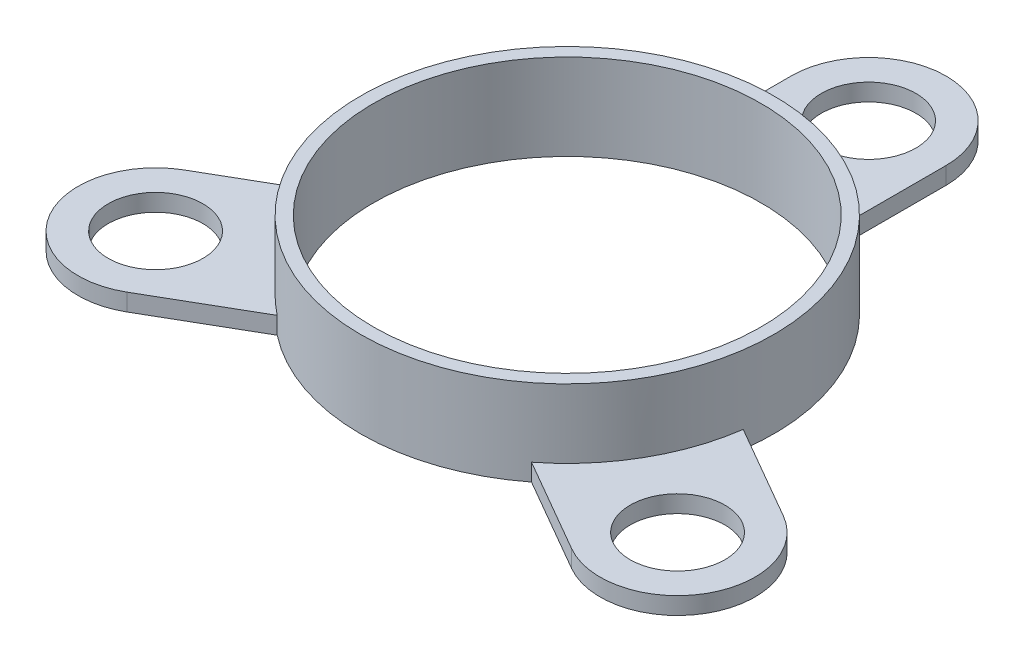
SolidWorks part; units mm, degrees
ref_plane "Front Plane" through (0, 0, 0) normal (0, 0, 1) x (1, 0, 0)
ref_plane "Top Plane" through (0, 0, 0) normal (0, 1, 0) x (1, 0, 0)
ref_plane "Right Plane" through (0, 0, 0) normal (1, 0, 0) x (0, 0, -1)
sketch "Sketch1" plane through (0, 0, 0) normal (0, 1, 0) x (1, 0, 0)
  line L0 (0, 0) -> (0, 22) construction
  line L1 (17.4054, -4.8529) -> (11.8839, -1.665)
  line L2 (12.9054, -12.6471) -> (7.3839, -9.4593)
  line L3 (-4.5, 17.5) -> (-4.5, 11.1243)
  line L4 (4.5, 17.5) -> (4.5, 11.1243)
  line L5 (-12.9054, -12.6471) -> (-7.3839, -9.4593)
  line L6 (-17.4054, -4.8529) -> (-11.8839, -1.665)
  circle A0 centre (0, 0) radius 22
  circle A1 centre (0, 0) radius 11.25
  circle A2 centre (0, 0) radius 4
  circle A3 centre (0, 0) radius 17.5 construction
  arc A4 (12.9054, -12.6471) -> (17.4054, -4.8529) centre (15.1554, -8.75) ccw
  circle A5 centre (15.1554, -8.75) radius 2.75
  circle A6 centre (0, 17.5) radius 2.75 construction
  arc A7 (-17.4054, -4.8529) -> (-12.9054, -12.6471) centre (-15.1554, -8.75) ccw
  circle A8 centre (-15.1554, -8.75) radius 2.75
  arc A9 (4.5, 17.5) -> (-4.5, 17.5) centre (0, 17.5) ccw
  circle A10 centre (0, 0) radius 12
  circle A12 centre (0, 17.5) radius 2.75
  point P8 (0, 0)
  point P9 (0, 17.5)
  point P29 (0.0281, 0.078)
  point P32 (0, 0)
extrude "Boss-Extrude1" add sketch "Sketch1" along normal blind 1 contours A10 | A10 L4 A9 L3 A12 | A10 region at (19.3391, 0, 7.629) region at (-19.3391, 0, 7.629) region at (0, 0, -12.1412)
extrude "Boss-Extrude2" add sketch "Sketch1<4>" along normal blind 5 contours A10 A1 region at (10.0984, 0, 5.8303)
sketch "Sketch1<4>" plane through (0, 0, 0) normal (0, 1, 0) x (1, 0, 0) same geometry as "Sketch1"
